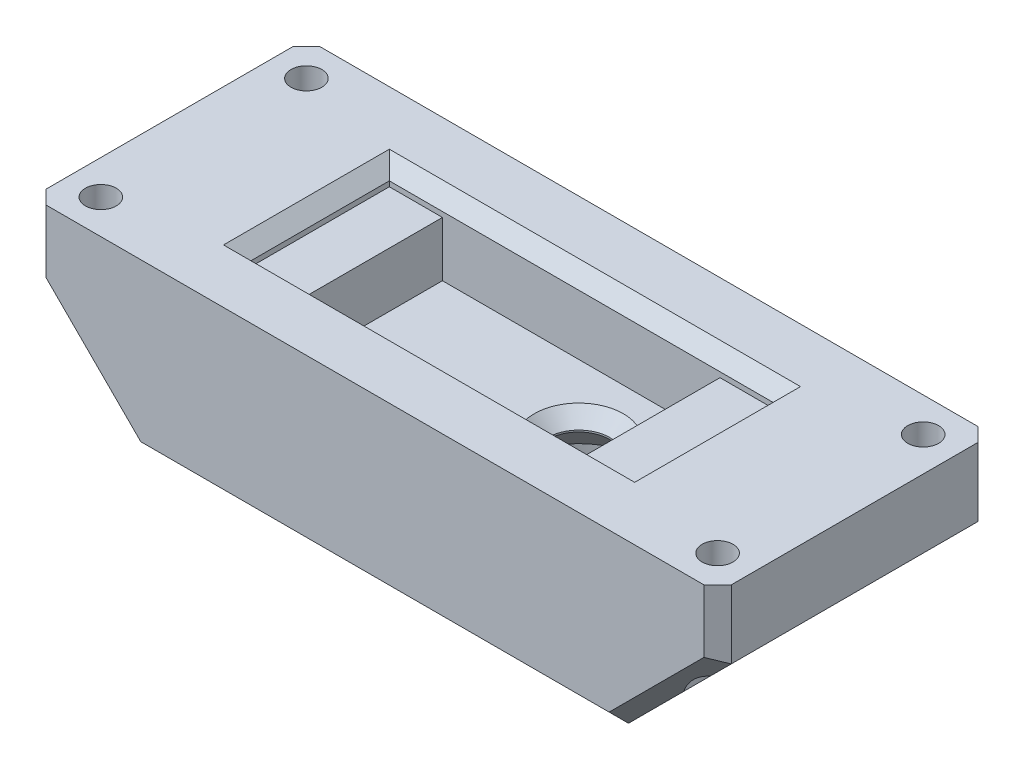
SolidWorks part; units mm, degrees
ref_plane "Front Plane" through (0, 0, 0) normal (0, 0, 1) x (1, 0, 0)
ref_plane "Top Plane" through (0, 0, 0) normal (0, 1, 0) x (1, 0, 0)
ref_plane "Right Plane" through (0, 0, 0) normal (1, 0, 0) x (0, 0, -1)
sketch "Sketch1" plane through (0, 0, 0) normal (0, 1, 0) x (1, 0, 0)
  line L0 (-50, 0) -> (50, 0) construction
  line L1 (-50, -20) -> (-50, 20)
  line L2 (-50, 20) -> (50, 20)
  line L3 (50, 20) -> (50, -20)
  line L4 (50, -20) -> (-50, -20)
  point P4 (0, 0)
  point P8 (-50, 0)
  dimension "D1" = 100
  dimension "D2" = 40
extrude "Boss-Extrude1" add sketch "Sketch1" along normal blind 25
sketch "Sketch2" plane through (0, 0, 0) normal (0, 1, 0) x (1, 0, 0)
  line L0 (-50, -20) -> (-50, -15) construction
  line L1 (-50, 20) -> (-50, -20) construction
  line L2 (-50, -15) -> (-45, -15) construction
  line L3 (-45, -15) -> (-45, 15) construction
  circle A0 centre (-45, -15) radius 2.25
  circle A1 centre (-45, 15) radius 2.25
  dimension "D3" = 4.5
  dimension "D5" = 4.5
  dimension "D1" = 5
  dimension "D2" = 5
  dimension "D4" = 30
extrude "Cut-Extrude1" cut sketch "Sketch2" along normal blind 25
mirror "Mirror1" about plane through (0, 0, 0) normal (1, 0, 0) of "Cut-Extrude1"
sketch "Sketch3" plane through (0, 0, 0) normal (0, 1, 0) x (1, 0, 0)
  circle A0 centre (-45, 15) radius 3.55
  circle A1 centre (-45, -15) radius 3.55
  dimension "D1" = 7.1
  dimension "D2" = 7.1
extrude "Cut-Extrude2" cut sketch "Sketch3" along normal blind 20
mirror "Mirror2" about plane through (0, 0, 0) normal (1, 0, 0) of "Cut-Extrude2"
ref_plane "Plane1" through (0, 25, 0) normal (0, 1, 0) x (1, 0, 0)
sketch "Sketch4" plane through (0, 25, 0) normal (0, 1, 0) x (1, 0, 0)
  line L0 (-28, 0) -> (28, 0) construction
  line L1 (-28, -10.1) -> (-28, 10.1)
  line L2 (-28, 10.1) -> (28, 10.1)
  line L3 (28, 10.1) -> (28, -10.1)
  line L4 (28, -10.1) -> (-28, -10.1)
  point P4 (0, 0)
  point P8 (-28, 0)
  dimension "D1" = 56
  dimension "D2" = 20.2
extrude "Cut-Extrude3" cut sketch "Sketch4" against normal blind 2.75
sketch "Sketch5" plane through (0, 25, 0) normal (0, 1, 0) x (1, 0, 0)
  line L0 (-20.25, 0) -> (20.25, 0) construction
  line L1 (-20.25, -10.1) -> (-20.25, 10.1)
  line L2 (28, 10.1) -> (-28, 10.1) construction
  line L3 (-20.25, 10.1) -> (20.25, 10.1)
  line L4 (20.25, 10.1) -> (20.25, -10.1)
  line L5 (-28, -10.1) -> (28, -10.1) construction
  line L6 (20.25, -10.1) -> (-20.25, -10.1)
  point P4 (0, 0)
  point P10 (-20.25, 0)
  dimension "D1" = 40.5
extrude "Cut-Extrude4" cut sketch "Sketch5" against normal blind 10.75
sketch "Sketch6" plane through (0, 25, 0) normal (0, 1, 0) x (1, 0, 0)
  line L0 (-20.25, 0) -> (9.75, 0) construction
  line L1 (-20.25, -10.1) -> (-20.25, 10.1) construction
  circle A0 centre (9.75, 0) radius 4.5
  dimension "D2" = 9
  dimension "D1" = 30
extrude "Cut-Extrude5" cut sketch "Sketch6" against normal through all
sketch "Sketch7" plane through (0, 0, 0) normal (0, 1, 0) x (1, 0, 0)
  circle A0 centre (9.75, 0) radius 11
  dimension "D1" = 22
extrude "Cut-Extrude6" cut sketch "Sketch7" along normal blind 7
chamfer "Chamfer1" distance 5 1 edges at (9.75, 7, 4.5)
chamfer "Chamfer2" distance 15 2 edges at (-50, 0, 0) (50, 0, 0)
chamfer "Chamfer3" distance 2 10 edges at (50, 20, -20) (42.5, 7.5, -20) (0, 0, -20) (-42.5, 7.5, -20) (-50, 20, -20) (-50, 20, 20) (-42.5, 7.5, 20) (0, 0, 20) (42.5, 7.5, 20) (50, 20, 20)
ref_plane "Plane2" through (0, 0, 0) normal (0, 0, 1) x (1, 0, 0)
sketch "Sketch8" plane through (0, 0, 0) normal (0, 0, 1) x (1, 0, 0)
  line L0 (9.75, 14.25) -> (9.75, 7) construction
  line L1 (14.25, 14.25) -> (5.25, 14.25) construction
  line L2 (0.25, 7) -> (19.25, 7) construction
  line L3 (9.75, 7) -> (9.75, 0) construction
  line L4 (-1.25, 0) -> (20.75, 0) construction
chamfer "Chamfer4" distance 2 1 edges at (9.75, 14.25, -4.5)
chamfer "Chamfer5" distance 2 4 edges at (0, 25, -10.1) (-28, 25, 0) (0, 25, 10.1) (28, 25, 0)
